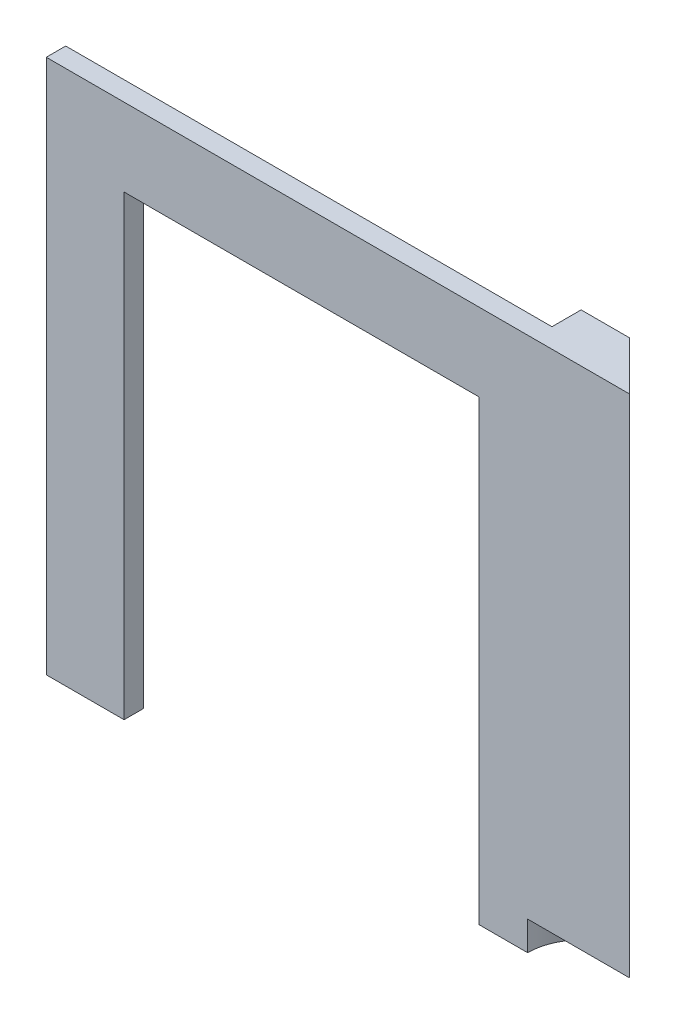
SolidWorks part; units mm, degrees
ref_plane "Plan de face" through (0, 0, 0) normal (0, 0, 1) x (1, 0, 0)
ref_plane "Plan de dessus" through (0, 0, 0) normal (0, 1, 0) x (1, 0, 0)
ref_plane "Plan de droite" through (0, 0, 0) normal (1, 0, 0) x (0, 0, -1)
sketch "Esquisse1" plane through (0, 0, 0) normal (0, 1, 0) x (1, 0, 0)
  line L0 (34, -2.5) -> (29, 2.5)
  line L1 (29, 2.5) -> (18.5, 2.5)
  line L2 (18.5, 2.5) -> (18.5, -0.5)
  line L3 (-26, -2.5) -> (34, -2.5)
  line L4 (18.5, -0.5) -> (-26, -0.5)
  line L5 (-26, -0.5) -> (-26, -2.5)
  dimension "D1" = 44.5
  dimension "D2" = 225
  dimension "D3" = 2
  dimension "D4" = 5
  dimension "D5" = 10.5
extrude "Boss.-Extru.1" add sketch "Esquisse1" along normal blind 55
sketch "Esquisse2" plane through (0, 0, 0.5) normal (0, 0, -1) x (-1, 0, 0)
  line L0 (26, 55) -> (26, 0) construction
  line L1 (-18.5, 0) -> (18, 0)
  line L2 (-18.5, 0) -> (-18.5, 47)
  line L3 (-18.5, 47) -> (18, 47)
  line L4 (18, 0) -> (18, 47)
  line L5 (-18.5, 55) -> (26, 55) construction
  dimension "D1" = 8
  dimension "D2" = 8
extrude "Enlèv. mat.-Extru.1" cut sketch "Esquisse2" against normal through all
sketch "Esquisse3" plane through (0, 0, -2.5) normal (0, 0, -1) x (-1, 0, 0)
  line L0 (18, 47) -> (-18.5, 47) construction
  line L1 (-18.5, 55) -> (-24, 55)
  line L2 (-18.5, 55) -> (-18.5, 47)
  line L3 (-18.5, 47) -> (-24, 47)
  line L4 (-24, 55) -> (-24, 47)
  line L5 (-34, 55) -> (-34, 0) construction
  dimension "D1" = 10
extrude "Enlèv. mat.-Extru.2" cut sketch "Esquisse3" against normal up to surface (3 mm away) up to face at (-8.5, 34, 0.5)
sketch "Esquisse4" plane through (0, 0, 0) normal (0, -1, 0) x (1, 0, 0)
  circle A0 centre (29, 2.5) radius 5.5
  arc A1 (34, 4.7913) -> (26.7087, -2.5) centre (29, 2.5) ccw construction
extrude "Enlèv. mat.-Extru.3" cut sketch "Esquisse4" against normal blind 3
